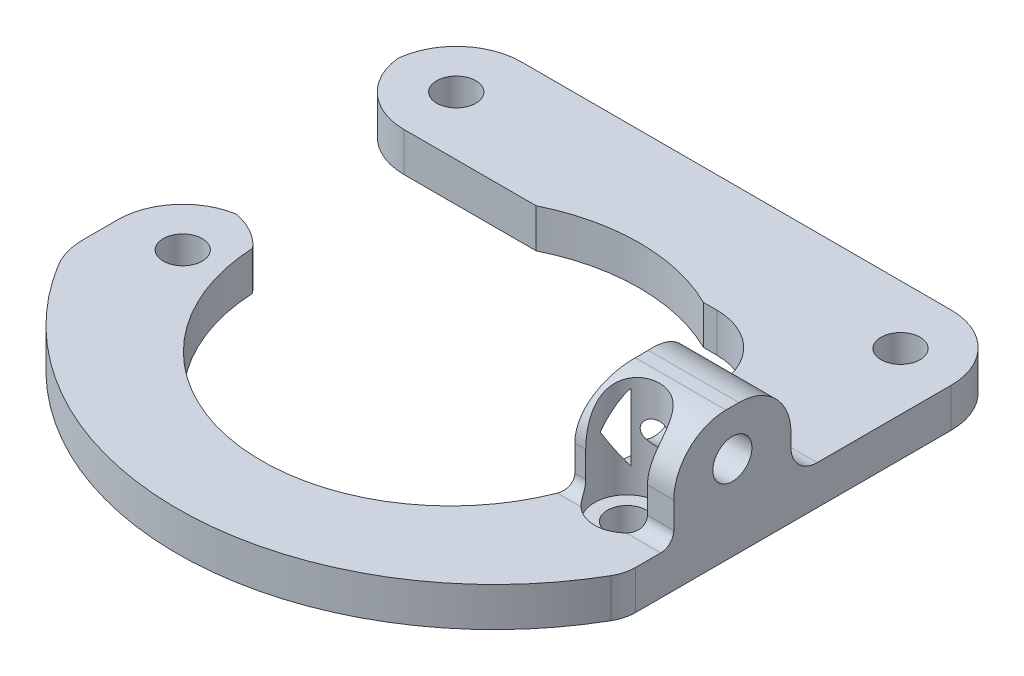
SolidWorks part; units mm, degrees
ref_plane "Plan de face" through (0, 0, 0) normal (0, 0, 1) x (1, 0, 0)
ref_plane "Plan de dessus" through (0, 0, 0) normal (0, 1, 0) x (1, 0, 0)
ref_plane "Plan de droite" through (0, 0, 0) normal (1, 0, 0) x (0, 0, -1)
sketch "Esquisse1" plane through (0, 0, 0) normal (0, 1, 0) x (1, 0, 0)
  line L0 (-43.062, 37.5582) -> (-43.062, 28.5582)
  line L1 (-43.062, 28.5582) -> (-9.062, 28.5582)
  line L2 (-9.062, 28.5582) -> (-9.062, 16.5582)
  line L3 (-9.062, 16.5582) -> (-10.4007, 16.5582)
  line L4 (-34.6083, 16.5582) -> (-43.062, 16.5582)
  line L5 (-43.062, 16.5582) -> (-43.062, 7.5582)
  line L7 (-0.062, 7.5582) -> (-0.062, 37.5582)
  line L8 (-0.062, 37.5582) -> (-43.062, 37.5582)
  line L9 (-38.562, 12.0582) -> (-4.452, 12.0582) construction
  arc A0 (-34.6083, 16.5582) -> (-10.4007, 16.5582) centre (-22.5045, 13.8776) ccw
  circle A1 centre (-38.562, 33.0582) radius 1.5
  circle A2 centre (-4.452, 33.0582) radius 1.5
  circle A3 centre (-38.562, 12.0582) radius 1.5
  circle A4 centre (-4.452, 12.0582) radius 1.5
  arc A5 (-43.062, 7.5582) -> (-0.062, 7.5582) centre (-21.562, 18.9935) ccw
  dimension "D3" = 3
  dimension "D4" = 3
  dimension "D5" = 3
  dimension "D6" = 3
  dimension "D7" = 4.5
  dimension "D9" = 34.11
  dimension "D10" = 0
  dimension "D11" = 34.11
  dimension "D12" = 4.5
  dimension "D13" = 4.5
  dimension "D14" = 0
  dimension "D1" = 43
  dimension "D2" = 43
  dimension "D15" = 9
  dimension "D16" = 9
  dimension "D17" = 21
  dimension "D18" = 9
extrude "Boss.-Extru.1" add sketch "Esquisse1" along normal blind 3
fillet "Congé1" radius 5 6 edges at (-10.4007, 1.5, -16.5582) (-34.6083, 1.5, -16.5582) (-43.062, 1.5, -37.5582) (-43.062, 1.5, -28.5582) (-43.062, 1.5, -16.5582) (-43.062, 1.5, -7.5582)
sketch "Esquisse2" plane through (0, 3, 0) normal (0, 1, 0) x (1, 0, 0)
  line L0 (-9.062, 28.5582) -> (-9.062, 16.5582) construction
  line L1 (-9.062, 20.2582) -> (-0.062, 20.2582)
  line L2 (-9.062, 20.2582) -> (-9.062, 11.2582)
  line L3 (-9.062, 11.2582) -> (-0.062, 11.2582)
  line L4 (-0.062, 20.2582) -> (-0.062, 11.2582)
  line L5 (-9.062, 20.2582) -> (-0.062, 11.2582) construction
  line L6 (-9.062, 11.2582) -> (-0.062, 20.2582) construction
  line L7 (-0.062, 7.5582) -> (-0.062, 37.5582) construction
  circle A0 centre (-4.452, 12.0582) radius 1.5 construction
  point P4 (-4.562, 15.7582)
  dimension "D1" = 3.7
  dimension "D2" = 9
extrude "Boss.-Extru.2" add sketch "Esquisse2" along normal blind 7
sketch "Esquisse3" plane through (0, 10, 0) normal (0, 1, 0) x (1, 0, 0)
  circle A0 centre (-4.452, 12.0582) radius 2.5
  dimension "D1" = 5
extrude "Enlèv. mat.-Extru.1" cut sketch "Esquisse3" against normal up to surface (7 mm away) up to face at (-19.9179, 3, -9.6055)
sketch "Esquisse6" plane through (-9.062, 0, 0) normal (-1, 0, 0) x (0, 0, 1)
  line L0 (-11.2582, 10) -> (-11.2582, 3) construction
  line L1 (-28.5582, 3) -> (-20.2582, 3) construction
  circle A0 centre (-15.7582, 6.5) radius 1.5
  dimension "D1" = 4.5
  dimension "D2" = 3
  dimension "D3" = 3.5
extrude "Enlèv. mat.-Extru.2" cut sketch "Esquisse6" against normal through all
sketch "Esquisse7" plane through (-9.062, 0, 0) normal (-1, 0, 0) x (0, 0, 1)
  line L1 (-14.1142, 3.6492) -> (-12.4673, 6.4984)
  line L2 (-12.4673, 6.4984) -> (-14.1114, 9.3492)
  line L3 (-14.1114, 9.3492) -> (-17.4023, 9.3508)
  line L4 (-17.4023, 9.3508) -> (-19.0491, 6.5016)
  line L5 (-19.0491, 6.5016) -> (-17.405, 3.6508)
  line L6 (-17.405, 3.6508) -> (-14.1142, 3.6492)
  circle A0 centre (-15.7582, 6.5) radius 2.85 construction
  dimension "D1" = 5.7
extrude "Enlèv. mat.-Extru.3" cut sketch "Esquisse7" against normal blind 3
fillet "Congé2" radius 5 2 edges at (-9.062, 1.5, -28.5582) (-0.062, 1.5, -37.5582)
fillet "Congé5" radius 2 1 edges at (-4.562, 3, -20.2582) type face fillet first side face at (-4.562, 6.5, -20.2582) second side face at (-17.355, 3, -29.3328)
fillet "Congé7" radius 4 1 edges at (-4.562, 10, -20.2582)
fillet "Congé8" radius 4 1 edges at (-7.9413, 10, -11.2582)
fillet "Congé10" radius 1 2 edges at (-1.0727, 3, -11.2582) (-7.9413, 3, -11.2582)
fillet "Congé11" radius 3 1 edges at (-0.062, 1.5, -7.5582)
sketch "Esquisse8" plane through (0, 3, 0) normal (0, 1, 0) x (1, 0, 0)
  circle A0 centre (-4.452, 12.0582) radius 2.5
extrude "Enlèv. mat.-Extru.4" cut sketch "Esquisse8" against normal blind 1
sketch "Esquisse9" plane through (0, 3, 0) normal (0, 1, 0) x (1, 0, 0)
  line L0 (-38.562, 12.0582) -> (-4.452, 12.0582) construction
  line L1 (-21.507, 12.0582) -> (-21.507, 15.5582) construction
  circle A0 centre (-21.507, 15.5582) radius 14.5
  dimension "D2" = 29
  dimension "D1" = 3.5
extrude "Enlèv. mat.-Extru.5" cut sketch "Esquisse9" against normal through all and the other way through all
